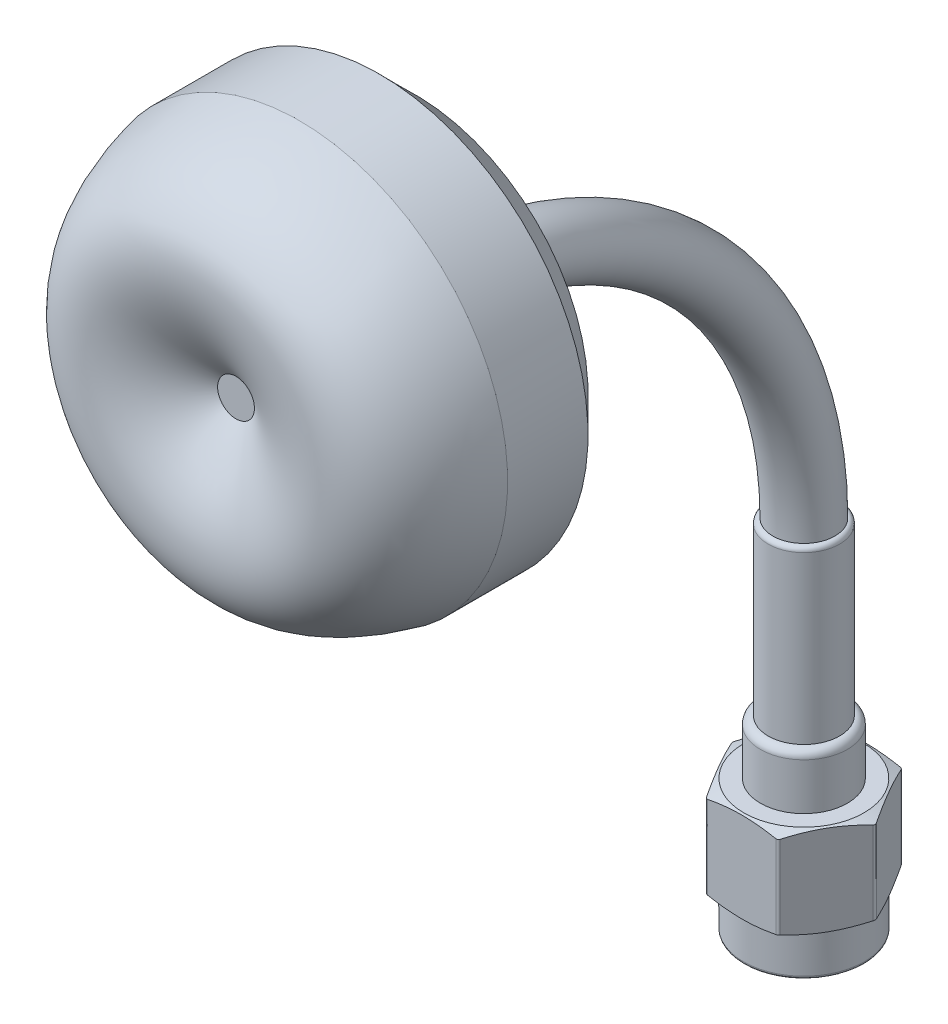
SolidWorks part; units mm, degrees
ref_plane "Front Plane" through (0, 0, 0) normal (0, 0, 1) x (1, 0, 0)
ref_plane "Top Plane" through (0, 0, 0) normal (0, 1, 0) x (1, 0, 0)
ref_plane "Right Plane" through (0, 0, 0) normal (1, 0, 0) x (0, 0, -1)
sketch "Sketch1" plane through (0, 0, 0) normal (0, 1, 0) x (1, 0, 0)
  circle A0 centre (0, 0) radius 3.88
  dimension "D1" = 7.76
extrude "Boss-Extrude1" add sketch "Sketch1" along normal blind 2.6
ref_axis "Axis1" through (0, 2.6, 0) along (0, -1, 0)
sketch "Sketch2" plane through (0, 2.6, 0) normal (0, 1, 0) x (1, 0, 0)
  line L1 (-2.3094, -4) -> (2.3094, -4)
  line L2 (2.3094, -4) -> (4.6188, 0)
  line L3 (4.6188, 0) -> (2.3094, 4)
  line L4 (2.3094, 4) -> (-2.3094, 4)
  line L5 (-2.3094, 4) -> (-4.6188, 0)
  line L6 (-4.6188, 0) -> (-2.3094, -4)
  circle A0 centre (0, 0) radius 4 construction
  dimension "D1" = 8
extrude "Boss-Extrude2" add sketch "Sketch2" along normal blind 5.9
sketch "Sketch3" plane through (0, 0, 0) normal (0, -1, 0) x (1, 0, 0)
  circle A0 centre (0, 0) radius 3.25
  dimension "D1" = 6.5
extrude "Cut-Extrude1" cut sketch "Sketch3" against normal blind 1
sketch "Sketch4" plane through (0, 1, 0) normal (0, -1, 0) x (1, 0, 0)
  circle A0 centre (0, 0) radius 2.85
  circle A1 centre (0, 0) radius 0.475
  dimension "D1" = 5.7
  dimension "D2" = 0.95
extrude "Cut-Extrude2" cut sketch "Sketch4" against normal blind 2.45
sketch "Sketch5" plane through (0, 3.45, 0) normal (0, -1, 0) x (1, 0, 0)
  circle A0 centre (0, 0) radius 2.6
  circle A1 centre (0, 0) radius 2.85
  circle A2 centre (0, 0) radius 2.85
  dimension "D2" = 0.25
  dimension "D1" = 0
extrude "Cut-Extrude3" cut sketch "Sketch5" against normal blind 4
sketch "Sketch6" plane through (0, 3.45, 0) normal (0, -1, 0) x (1, 0, 0)
  circle A0 centre (0, 0) radius 0.475 construction
  circle A1 centre (0, 0) radius 0.475
  circle A4 centre (0, 0) radius 2.5
  circle A5 centre (0, 0) radius 2.5
  dimension "D1" = 0.1
extrude "Cut-Extrude4" cut sketch "Sketch6" against normal blind 0.1
thread "Thread1" pitch 1 method cut profile "Thread Profile1" start angle 0, offset 1, length 0, pitch 1, diameter 5.7
ref_plane "Plane1" through (2.85, 0, 0) normal (0, 0, 1) x (1, 0, 0)
sketch "Thread Profile1" plane through (2.85, 0, 0) normal (0, 0, 1) x (1, 0, 0)
  line L0 (0, 0) -> (0, 1) construction
  line L1 (0, 0) -> (0.5413, 0.3125)
  line L2 (0.5413, 0.3125) -> (0.5413, 0.4375)
  line L3 (0.5413, 0.4375) -> (0, 0.75)
  line L4 (0.5413, 0.375) -> (0, 0.375) construction
  line L11 (0, 0) -> (0, 0.75)
  point P2 (0, 0)
  dimension "Pitch" = 1
  dimension "Profile_Angle" = 60
  dimension "Profile_Land" = 0.125
  dimension "Profile_Height" = 0.5413
chamfer "Chamfer1" distance 1 angle 20 1 edges at (0, 1, -0.475) first distance on face at (0, 1, -0.475)
ref_plane "Plane2" through (0, 0, 0) normal (-0.866, 0, 0.5) x (0.5, 0, 0.866)
sketch "Sketch10" plane through (0, 0, 0) normal (-0.866, 0, 0.5) x (0.5, 0, 0.866)
  line L0 (-3.8688, 8.5) -> (-4.6188, 8.2)
  line L1 (-4.6188, 8.5) -> (-2.3094, 8.5) construction
  line L2 (-4.6188, 8.5) -> (-4.6188, 2.6) construction
  line L3 (-4.6188, 8.2) -> (-4.6188, 8.5)
  line L4 (-4.6188, 8.5) -> (-3.8688, 8.5)
  line L5 (-4.6188, 5.55) -> (4.6188, 5.55) construction
  line L6 (4.6188, 8.5) -> (4.6188, 2.6) construction
  line L7 (-4.6188, 2.9) -> (-4.6188, 2.6)
  line L8 (-3.8688, 2.6) -> (-4.6188, 2.9)
  line L9 (-4.6188, 2.6) -> (-3.8688, 2.6)
  dimension "D1" = 0.75
  dimension "D2" = 0.3
revolve "Cut-Revolve1" cut sketch "Sketch10" angle 360 about axis through (0, 2.6, 0) along (0, -1, 0)
fillet "Fillet1" radius 0.2 8 edges at (4.6188, 5.55, 0) (2.3094, 5.55, -4) (-2.3094, 5.55, -4) (0, 0, -3.25) (0, 0, 3.88) (2.3094, 5.55, 4) (-2.3094, 5.55, 4) (-4.6188, 5.55, 0)
sketch "Sketch11" plane through (0, 8.5, 0) normal (0, 1, 0) x (1, 0, 0)
  circle A0 centre (0, 0) radius 2.8
  dimension "D1" = 5.6
extrude "Boss-Extrude3" add sketch "Sketch11" along normal blind 3.5
sketch "Sketch12" plane through (0, 12, 0) normal (0, 1, 0) x (1, 0, 0)
  circle A0 centre (0, 0) radius 2.3
  dimension "D1" = 4.6
extrude "Boss-Extrude4" add sketch "Sketch12" along normal blind 11
sketch "Sketch17" plane through (0, 0, 0) normal (1, 0, 0) x (0, 0, -1)
  line L0 (0, 23) -> (0, 48) construction
  line L1 (2.3, 23) -> (-2.3, 23) construction
  line L2 (0, 48) -> (-25, 48) construction
  arc A0 (-25, 48) -> (0, 23) centre (-25, 23) cw
  point P8 (-8.8852, 33.9049)
  point P9 (0, 23.4169)
  dimension "D1" = 25
  dimension "D2" = 25
sketch "Sketch18" plane through (0, 23, 0) normal (0, 1, 0) x (1, 0, 0)
  circle A0 centre (0, 0) radius 2
  dimension "D1" = 4
sweep "Sweep1" add profiles "Sketch18" path "Sketch17"
ref_plane "Plane3" through (0, 0, 25) normal (0, 0, 1) x (1, 0, 0)
sketch "Sketch19" plane through (0, 0, 25) normal (0, 0, 1) x (1, 0, 0)
  line L0 (-2, 48) -> (2, 48) construction
  line L1 (0, 46) -> (0, 50) construction
  circle A0 centre (0, 48) radius 2 construction
ref_plane "Plane4" through (0, 48, 0) normal (0, -1, 0) x (1, 0, 0)
ref_point "Point1"
ref_axis "Axis2" through (0, 48, 25) along (0, 0, 1)
fillet "Fillet2" radius 0.5 1 edges at (0, 12, 2.8)
fillet "Fillet3" radius 0.3 1 edges at (0, 23, 2.3)
sketch "Sketch15" plane through (0, 48, 48) normal (0, 1, 0) x (1, 0, 0)
  line L13 (0, 23) -> (0, 11.438)
  line L14 (-2, 23) -> (2, 23) construction
  line L15 (0, 23) -> (0, 9.4756) construction
  line L16 (0, 11.438) -> (-1.1858, 11.438)
  line L17 (0, 23) -> (-11.0997, 23)
  line L18 (-9.7895, 23) -> (9.7895, 23) construction
  line L19 (-11.0997, 23) -> (-13.4153, 20.6845)
  line L20 (-13.4153, 20.6845) -> (-13.4153, 15.5112)
  spline S1 degree 2 poles (-13.4153, 15.5112) (-10.8676, 4.4766) (-1.1858, 11.438) knots 0 0 0 1 1 1
  point P0 (-1.1858, 11.438)
revolve "Revolve1" add sketch "Sketch15" angle 360 about axis through (0, 48, 25) along (0, 0, 1) region at (-6.5467, 48, 31.5705)
